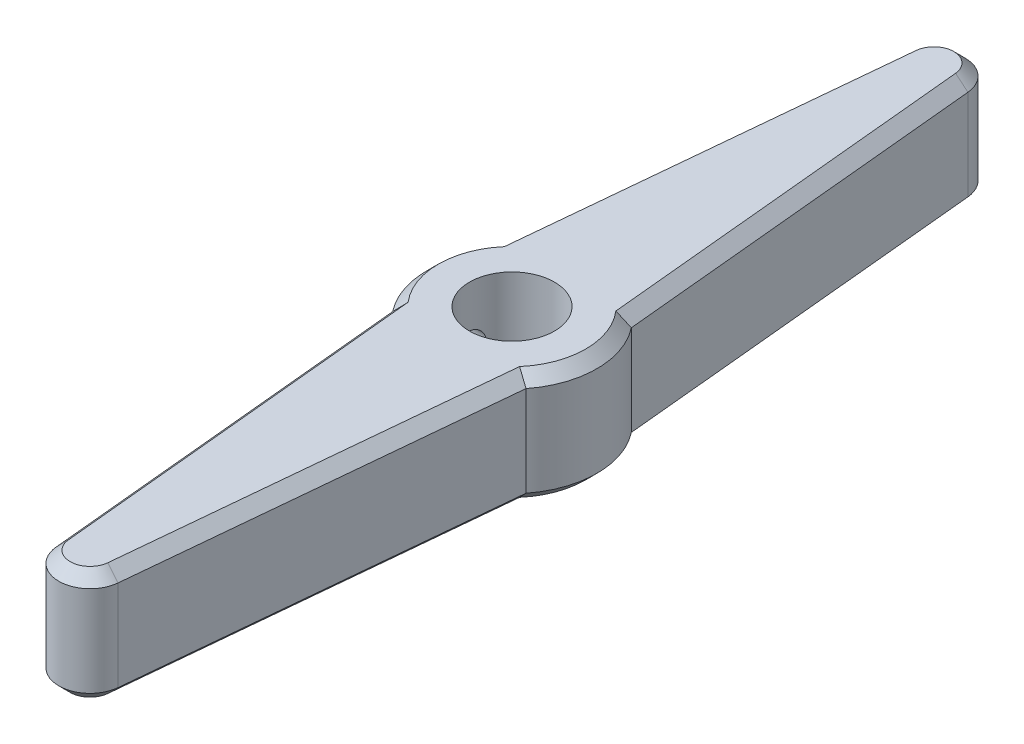
SolidWorks part; units mm, degrees
ref_plane "Front Plane" through (0, 0, 0) normal (0, 0, 1) x (1, 0, 0)
ref_plane "Top Plane" through (0, 0, 0) normal (0, 1, 0) x (1, 0, 0)
ref_plane "Right Plane" through (0, 0, 0) normal (1, 0, 0) x (0, 0, -1)
sketch "Sketch1" plane through (0, 0, 0) normal (0, 1, 0) x (1, 0, 0)
  circle A0 centre (0, 0) radius 4.7625
  circle A1 centre (0, 0) radius 9.525
  dimension "D1" = 9.525
  dimension "D2" = 19.05
extrude "Boss-Extrude1" add sketch "Sketch1" along normal mid plane 12.7 contours A1
sketch "Sketch2" plane through (0, 0, 0) normal (0, 1, 0) x (1, 0, 0)
  line L0 (-8.04, 0) -> (8.04, 0)
  line L1 (0, 0) -> (0, 50.8) construction
  line L2 (-3.175, 50.8) -> (3.175, 50.8)
  line L3 (3.175, 50.8) -> (8.04, 0)
  line L4 (-3.175, 50.8) -> (-8.04, 0)
  point P5 (0, 0)
  point P11 (0, 50.8)
  dimension "D1" = 50.8
  dimension "D2" = 6.35
extrude "Boss-Extrude2" add sketch "Sketch2" along normal mid plane 12.7
fillet "Fillet1" 2 edges at (3.175, 0, -50.8) (-3.175, 0, -50.8) type full round first side face at (5.3248, 0, -28.3519) second side face at (-5.3248, 0, -28.3519) middle face at (0, 0, -50.8)
mirror "Mirror2" about plane through (0, 0, 0) normal (0, 0, 1) of "Fillet1", "Boss-Extrude2"
chamfer "Chamfer1" distance 1.27 angle 45 16 edges at (9.525, -6.35, 0) (5.4761, -6.35, -26.7717) (0, -6.35, -50.8) (-5.4761, -6.35, -26.7717) (-9.525, -6.35, 0) (-5.4761, -6.35, 26.7717) (0, -6.35, 50.8) (5.4761, -6.35, 26.7717) (-9.525, 6.35, 0) (-5.4761, 6.35, -26.7717) (0, 6.35, -50.8) (5.4761, 6.35, -26.7717) (9.525, 6.35, 0) (5.4761, 6.35, 26.7717) (0, 6.35, 50.8) (-5.4761, 6.35, 26.7717)
extrude "Cut-Extrude1" cut sketch "Sketch1<3>" against normal through all both and the other way through all contours A0
sketch "Sketch1<3>" plane through (0, 0, 0) normal (0, 1, 0) x (1, 0, 0) same geometry as "Sketch1"
sketch "Sketch3" plane through (0, 0, 0) normal (1, 0, 0) x (0, 0, -1)
  circle A0 centre (0, 0) radius 1.5875
  dimension "D1" = 3.175
extrude "Cut-Extrude2" cut sketch "Sketch3" against normal through all
equation "\"D_Bearing\" = 7 / 8in"
equation "\"Tol_Bearing\" = 0.05in"
equation "\"BearingHole\" = \"D_Bearing\"+\"Tol_Bearing\""
equation "\"ShaftDistance\" = 2.5in"
equation "\"SpokeDistance\" = 1.75in"
equation "\"NumShaft\" = 3"
equation "\"IntakeOpening\" = \"SpokeDistance\"+1.75in"
equation "\"SpokeLength\" = 2in"
